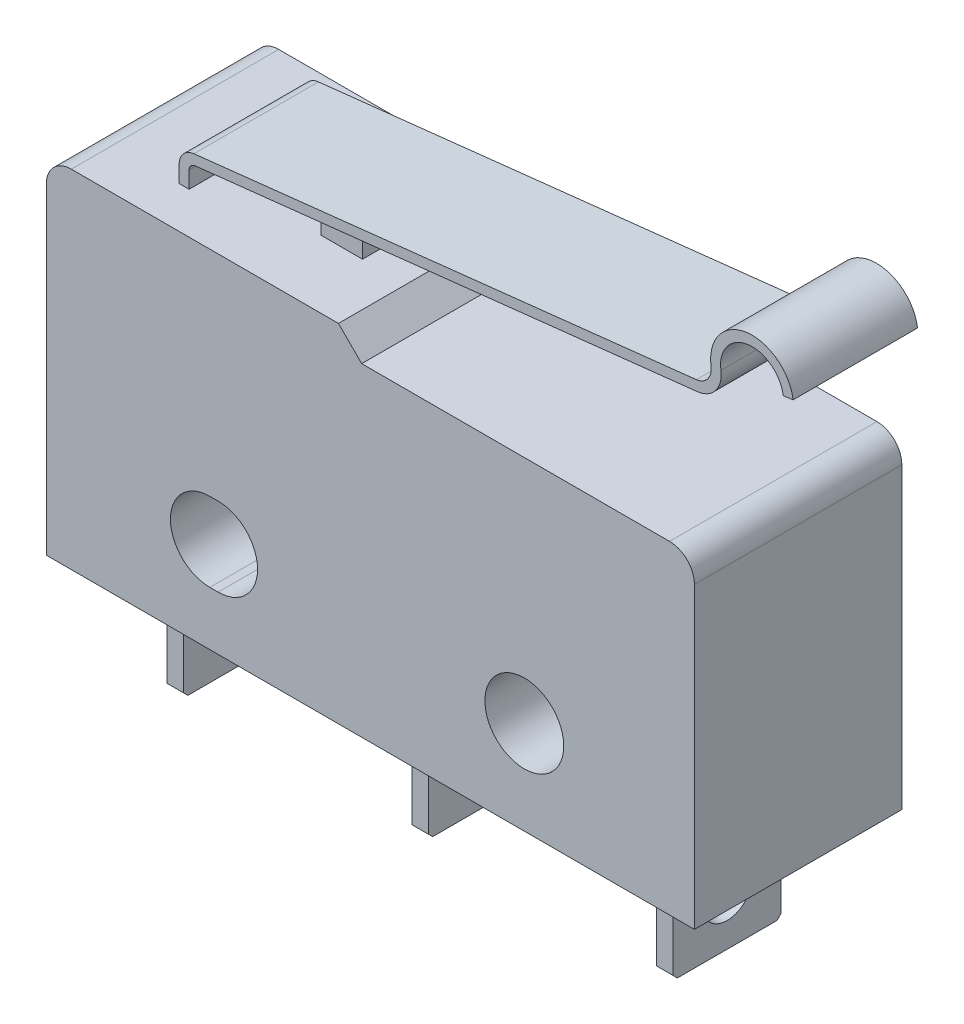
SolidWorks part; units mm, degrees
ref_plane "Front" through (0, 0, 0) normal (0, 0, 1) x (1, 0, 0)
ref_plane "Top" through (0, 0, 0) normal (0, 1, 0) x (1, 0, 0)
ref_plane "Right" through (0, 0, 0) normal (1, 0, 0) x (0, 0, -1)
sketch "Sketch2" plane through (0, 0, 0) normal (0, 0, 1) x (1, 0, 0)
  line L0 (-4.9149, 4.064) -> (-4.6609, 4.064)
  line L1 (-9.1567, 10.6172) -> (-4.9149, 10.6172)
  line L2 (-9.9187, 9.8552) -> (-9.9187, 0)
  line L3 (-9.9187, 0) -> (9.9187, 0)
  line L4 (9.9187, 9.144) -> (9.9187, 0)
  line L5 (-4.9149, 1.651) -> (-4.6609, 1.651)
  line L6 (-4.7879, 4.064) -> (-4.7879, 1.651) construction
  line L7 (4.7117, 2.8575) -> (-4.6609, 2.8575) construction
  line L8 (9.1567, 9.906) -> (-0.2667, 9.906)
  line L9 (-0.2667, 9.906) -> (-0.9779, 10.6172)
  line L10 (-0.9779, 10.6172) -> (-4.9149, 10.6172)
  line L13 (-2.9464, 10.6172) -> (-2.9464, 2.8575) construction
  line L14 (-4.9149, 10.6172) -> (-4.9149, 4.064) construction
  circle A0 centre (4.7117, 2.8575) radius 1.2065
  arc A1 (-4.9149, 4.064) -> (-4.9149, 1.651) centre (-4.9149, 2.8575) ccw
  arc A2 (-4.6609, 1.651) -> (-4.6609, 4.064) centre (-4.6609, 2.8575) ccw
  arc A3 (9.9187, 9.144) -> (9.1567, 9.906) centre (9.1567, 9.144) ccw
  arc A4 (-9.1567, 10.6172) -> (-9.9187, 9.8552) centre (-9.1567, 9.8552) ccw
  dimension "D4" = 5.207
  dimension "D5" = 2.413
  dimension "D6" = 2.667
  dimension "D7" = 9.906
  dimension "D8" = 10.6172
  dimension "D9" = 9.652
  dimension "D10" = 0.762
  dimension "D1" = 19.8374
  dimension "D2" = 2.8575
  dimension "D3" = 9.4996
  dimension "D12" = 135
extrude "Extrude1" add sketch "Sketch2" along normal mid plane 6.35
sketch "Sketch3" plane through (0, 0, 0) normal (0, 0, 1) x (1, 0, 0)
  line L0 (-3.5814, 10.6172) -> (-3.5814, 11.5246)
  line L1 (-2.9464, 10.6172) -> (-2.9464, 10.7315) construction
  line L2 (-2.3114, 11.5246) -> (-2.3114, 10.6172)
  line L3 (-2.3114, 10.6172) -> (-3.5814, 10.6172)
  line L4 (-3.5814, 11.5246) -> (-2.3114, 11.5246) construction
  line L5 (-2.9464, 10.6172) -> (-2.9464, 2.8575) construction
  line L7 (-0.9779, 10.6172) -> (-9.1567, 10.6172) construction
  arc A0 (-3.5814, 11.5246) -> (-2.3114, 11.5246) centre (-2.9464, 10.7315) cw
  arc A1 (-4.9149, 4.064) -> (-4.9149, 1.651) centre (-4.9149, 2.8575) ccw construction
  dimension "D1" = 8.89
  dimension "D3" = 1.016
  dimension "D2" = 1.27
extrude "Extrude2" add sketch "Sketch3" along normal mid plane 2.2098 separate body
ref_plane "Plane1" through (-7.493, 0, 0) normal (1, 0, 0) x (0, 0, -1)
sketch "Sketch10" plane through (-7.493, 0, 0) normal (1, 0, 0) x (0, 0, -1)
  line L0 (-1.651, 0) -> (-1.651, -3.0734)
  line L1 (-1.524, -3.2004) -> (1.524, -3.2004)
  line L2 (1.651, -3.0734) -> (1.651, 0)
  line L3 (1.651, 0) -> (-1.651, 0)
  line L4 (0, -3.2004) -> (0, -1.6764) construction
  line L5 (0, 0) -> (0, -1.6764) construction
  line L6 (-1.651, -3.0734) -> (-1.524, -3.2004)
  line L7 (1.524, -3.2004) -> (1.651, -3.0734)
  circle A0 centre (0, -1.6764) radius 0.762
  point P1 (-1.651, -3.2004)
  point P3 (1.651, -3.2004)
  dimension "D2" = 1.524
  dimension "D1" = 3.2004
  dimension "D3" = 3.302
  dimension "D4" = 1.524
  dimension "D5" = 0.127
  dimension "D6" = 45
  dimension "D7" = 0.127
  dimension "D8" = 45
extrude "Extrude6" add sketch "Sketch10" along normal mid plane 0.508
pattern_linear "LPattern1" count 3 spacing 7.493 along (1, 0, 0) of "Extrude6"
sketch "Sketch11" plane through (0, 0, 0) normal (0, 0, 1) x (1, 0, 0)
  line L0 (-7.1247, 10.6172) -> (-7.1247, 11.1283)
  line L1 (-0.9779, 10.6172) -> (-9.1567, 10.6172) construction
  line L2 (-6.6726, 11.6332) -> (8.7112, 13.335)
  line L3 (-9.9187, 9.8552) -> (-9.9187, 0) construction
  line L4 (-9.9187, 0) -> (9.9187, 0) construction
  line L5 (9.158, 13.9134) -> (11.6713, 14.2806) construction
  arc A0 (-7.1247, 11.1283) -> (-6.6726, 11.6332) centre (-6.6167, 11.1283) cw
  arc A1 (9.158, 13.9134) -> (11.6713, 14.2806) centre (10.4146, 14.097) cw
  arc A2 (8.7112, 13.335) -> (9.158, 13.9134) centre (8.6553, 13.8399) ccw
  dimension "D4" = 1.27
  dimension "D5" = 0.508
  dimension "D1" = 2.794
  dimension "D2" = 15.367
  dimension "D3" = 21.59
  dimension "D6" = 1.016
  dimension "D7" = 13.335
extrude "Extrude-Thin1" add sketch "Sketch11" along normal mid plane 3.81 thin thin type one direction wall 0.3048
